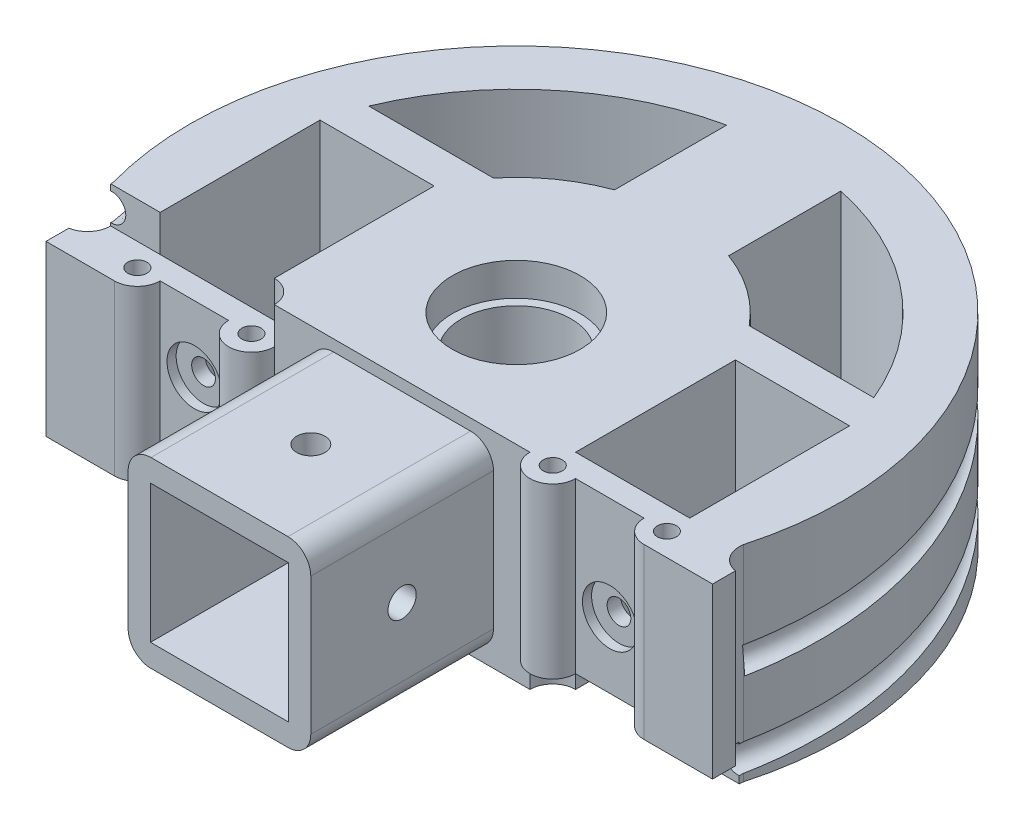
SolidWorks part; units mm, degrees
note: '?' marks a value the reader was unsure of.
ref_plane "Front Plane" through (0, 0, 0) normal (0, 0, 1) x (1, 0, 0)
ref_plane "Top Plane" through (0, 0, 0) normal (0, 1, 0) x (1, 0, 0)
ref_plane "Right Plane" through (0, 0, 0) normal (1, 0, 0) x (0, 0, -1)
sketch "Sketch1" plane through (0, 0, 0) normal (0, 1, 0) x (1, 0, 0)
  line L0 (0, 0) -> (-17.6777, -17.6777) construction
  line L1 (-17.6777, -17.6777) -> (-62.3934, 27.0381)
  line L2 (0, 68) -> (0, 0) construction
  line L3 (-38.8909, 3.5355) -> (30.8465, 73.2729) construction
  line L4 (-56.5685, 21.2132) -> (9.0638, 86.8455) construction
  line L5 (17.6777, -17.6777) -> (62.3934, 27.0381)
  line L6 (-51.6188, 26.163) -> (-33.9411, 8.4853)
  line L7 (-51.6188, 26.163) -> (-33.9411, 43.8406)
  line L8 (-33.9411, 8.4853) -> (-16.2635, 26.163)
  line L9 (-33.9411, 43.8406) -> (-16.2635, 26.163)
  line L10 (51.6188, 26.163) -> (33.9411, 43.8406)
  line L11 (51.6188, 26.163) -> (33.9411, 8.4853)
  line L12 (33.9411, 8.4853) -> (16.2635, 26.163)
  line L13 (33.9411, 43.8406) -> (16.2635, 26.163)
  circle A0 centre (0, 0) radius 68
  circle A1 centre (0, 0) radius 14.05
  circle A2 centre (0, 0) radius 25
  dimension "D1" = 136
  dimension "D2" = 28.1
  dimension "D3" = 50
  dimension "D4" = 30
  dimension "D5" = 25
  dimension "D6" = 7
  dimension "D7" = 25
  dimension "D8" = 25
extrude "Boss-Extrude1" add sketch "Sketch1" along normal blind 45 contours A2 A1 | A2 L5 A0 L1 L7 L9 L8 L6 L13 L10 L11 L12
sketch "Sketch2" plane through (0, 45, 0) normal (0, 1, 0) x (1, 0, 0)
  line L0 (-51.6188, 26.163) -> (-23.3345, 54.4472)
  line L1 (-51.6188, 26.163) -> (-33.9411, 8.4853)
  line L2 (-33.9411, 8.4853) -> (-5.6569, 36.7696)
  line L3 (-5.6569, 36.7696) -> (-23.3345, 54.4472)
  line L4 (0, 68) -> (0, -25) construction
  line L5 (33.9411, 8.4853) -> (5.6569, 36.7696)
  line L6 (51.6188, 26.163) -> (33.9411, 8.4853)
  line L7 (51.6188, 26.163) -> (23.3345, 54.4472)
  line L8 (5.6569, 36.7696) -> (23.3345, 54.4472)
  arc A0 (62.3934, 27.0381) -> (-62.3934, 27.0381) centre (0, 0) ccw construction
  arc A1 (-17.6777, -17.6777) -> (17.6777, -17.6777) centre (0, 0) ccw construction
  dimension "D1" = 40
  dimension "D2" = 40
extrude "Cut-Extrude1" cut sketch "Sketch2" against normal blind 45
sketch "Sketch3" plane through (0, 45, 0) normal (0, 1, 0) x (1, 0, 0)
  line L0 (-20.5061, 51.6188) -> (-48.7904, 23.3345)
  line L1 (-5.6569, 36.7696) -> (-23.3345, 54.4472) construction
  line L2 (-51.6188, 26.163) -> (-33.9411, 8.4853) construction
  line L3 (-48.7904, 23.3345) -> (-51.6188, 26.163)
  line L4 (-51.6188, 26.163) -> (-23.3345, 54.4472)
  line L5 (-23.3345, 54.4472) -> (-20.5061, 51.6188)
  line L6 (-33.9411, 8.4853) -> (-36.7696, 11.3137)
  line L7 (-36.7696, 11.3137) -> (-8.4853, 39.598)
  line L8 (-8.4853, 39.598) -> (-5.6569, 36.7696)
  line L9 (-5.6569, 36.7696) -> (-33.9411, 8.4853)
  line L10 (0, 68) -> (0, -25) construction
  line L11 (8.4853, 39.598) -> (5.6569, 36.7696)
  line L12 (36.7696, 11.3137) -> (8.4853, 39.598)
  line L13 (33.9411, 8.4853) -> (36.7696, 11.3137)
  line L14 (5.6569, 36.7696) -> (33.9411, 8.4853)
  line L15 (51.6188, 26.163) -> (23.3345, 54.4472)
  line L16 (48.7904, 23.3345) -> (51.6188, 26.163)
  line L17 (20.5061, 51.6188) -> (48.7904, 23.3345)
  line L18 (23.3345, 54.4472) -> (20.5061, 51.6188)
  arc A0 (62.3934, 27.0381) -> (-62.3934, 27.0381) centre (0, 0) ccw construction
  arc A1 (-17.6777, -17.6777) -> (17.6777, -17.6777) centre (0, 0) ccw construction
  dimension "D1" = 4
  dimension "D2" = 4
extrude "Boss-Extrude2" add sketch "Sketch3" against normal blind 45
chamfer "Chamfer1" distance 4 angle 45 4 edges at (34.6482, 45, -37.4767) (22.6274, 45, -25.4558) (-22.6274, 45, -25.4558) (-34.6482, 45, -37.4767)
chamfer "Chamfer2" distance 4 angle 45 4 edges at (34.6482, 0, -37.4767) (22.6274, 0, -25.4558) (-22.6274, 0, -25.4558) (-34.6482, 0, -37.4767)
sketch "Sketch5" plane through (0, 45, 0) normal (0, 1, 0) x (1, 0, 0)
  line L0 (-48.4659, 29.3158) -> (-68.4772, 9.3045) construction
  line L1 (-51.6188, 26.163) -> (-23.3345, 54.4472) construction
  line L2 (-30.0213, 12.4051) -> (-51.4271, -9.0007) construction
  line L3 (-5.6569, 36.7696) -> (-33.9411, 8.4853) construction
  line L4 (-17.6777, -17.6777) -> (-62.3934, 27.0381) construction
  line L5 (-42.78, 17.3241) -> (-61.4892, -1.3852) construction
  line L6 (-51.6188, 26.163) -> (-33.9411, 8.4853) construction
  line L7 (0, 68) -> (0, 30.851) construction
  circle A0 centre (-57.9828, 22.6274) radius 5
  circle A1 centre (-37.4767, 2.1213) radius 5
  arc A2 (62.3934, 27.0381) -> (-62.3934, 27.0381) centre (0, 0) ccw construction
  circle A3 centre (37.4767, 2.1213) radius 5
  circle A4 centre (57.9828, 22.6274) radius 5
  dimension "D1" = 10
  dimension "D2" = 2
extrude "Boss-Extrude4" add sketch "Sketch5" against normal up to surface (45 mm away) contours A0 | A1 | A4 | A3 up to face at (28.6378, 0, -31.4663)
sketch "Sketch6" plane through (0, 45, 0) normal (0, 1, 0) x (1, 0, 0)
  line L0 (-61.5183, 26.163) -> (-65.7609, 30.4056)
  line L1 (-65.7609, 30.4056) -> (-63.9013, 33.947)
  line L2 (-55.3925, 39.442) -> (-61.5183, 26.163)
  line L3 (0, 68) -> (0, 0) construction
  line L4 (65.7609, 30.4056) -> (63.9013, 33.947)
  line L5 (61.5183, 26.163) -> (65.7609, 30.4056)
  line L6 (55.3925, 39.442) -> (61.5183, 26.163)
  arc A0 (-63.9013, 33.947) -> (-55.3925, 39.442) centre (-66.3939, 47.142) ccw
  arc A1 (62.3934, 27.0381) -> (-62.3934, 27.0381) centre (0, 0) ccw construction
  arc A2 (63.9013, 33.947) -> (55.3925, 39.442) centre (66.3939, 47.142) cw
  dimension "D1" = 6
  dimension "D2" = 4
extrude "Boss-Extrude5" add sketch "Sketch6" against normal up to surface (45 mm away) contours L2 L0 L1 A0 | A2 L6 L5 L4 up to face at (0, 0, -11.4344)
sketch "Sketch7" plane through (0, 45, 0) normal (0, 1, 0) x (1, 0, 0)
  circle A0 centre (-57.9828, 22.6274) radius 2.1
  circle A1 centre (-37.4767, 2.1213) radius 2.1
  circle A3 centre (57.9828, 22.6274) radius 2.1
  circle A4 centre (37.4767, 2.1213) radius 2.1
  dimension "D1" = 4.2
  dimension "D2" = 4.2
  dimension "D3" = 4.2
  dimension "D4" = 4.2
extrude "Cut-Extrude2" cut sketch "Sketch7" against normal blind 45
sketch "Sketch9" plane through (0, 45, 0) normal (0, 1, 0) x (1, 0, 0)
  line L0 (34.4309, 8.975) -> (63.6627, 38.2069)
  line L1 (63.6627, 38.2069) -> (69.3196, 32.55)
  line L2 (69.3196, 32.55) -> (61.5183, 26.163)
  line L3 (54.4472, 19.0919) -> (42.78, 7.4246)
  line L4 (41.0122, 5.6569) -> (54.4472, 19.0919) construction
  line L5 (0, 68) -> (0, 24.5845) construction
  line L6 (-54.4472, 19.0919) -> (-42.78, 7.4246)
  line L7 (-69.3196, 32.55) -> (-61.5183, 26.163)
  line L8 (-63.6627, 38.2069) -> (-69.3196, 32.55)
  line L9 (-34.4309, 8.975) -> (-63.6627, 38.2069)
  arc A0 (34.4309, 8.975) -> (42.78, 7.4246) centre (37.4767, 2.1213) ccw
  arc A1 (54.4472, 19.0919) -> (61.5183, 26.163) centre (57.9828, 22.6274) ccw
  arc A2 (55.3925, 39.442) -> (-55.3925, 39.442) centre (0, 0) ccw construction
  arc A3 (-34.4309, 8.975) -> (-42.78, 7.4246) centre (-37.4767, 2.1213) cw
  arc A4 (-54.4472, 19.0919) -> (-61.5183, 26.163) centre (-57.9828, 22.6274) cw
  dimension "D1" = 15
  dimension "D2" = 8
extrude "Cut-Extrude5" cut sketch "Sketch9" against normal blind 4
sketch "Sketch10" plane through (0, 0, 0) normal (0, -1, 0) x (-1, 0, 0)
  line L0 (-34.4309, 8.975) -> (-64.7535, 39.2977)
  line L1 (-64.7535, 39.2977) -> (-71.1522, 32.899)
  line L2 (-71.1522, 32.899) -> (-62.9828, 22.6274)
  line L3 (-44.543, 4.6348) -> (-57.554, 17.6458)
  line L4 (0, -25) -> (0, 8.975) construction
  line L5 (71.1522, 32.899) -> (62.9828, 22.6274)
  line L6 (64.7535, 39.2977) -> (71.1522, 32.899)
  line L7 (34.4309, 8.975) -> (64.7535, 39.2977)
  line L8 (44.543, 4.6348) -> (57.554, 17.6458)
  arc A0 (-44.543, 4.6348) -> (-34.4309, 8.975) centre (-37.4767, 2.1213) ccw
  arc A1 (-62.9828, 22.6274) -> (-57.554, 17.6458) centre (-57.9828, 22.6274) ccw
  arc A4 (-17.6777, -17.6777) -> (17.6777, -17.6777) centre (0, 0) ccw construction
  arc A5 (44.543, 4.6348) -> (34.4309, 8.975) centre (37.4767, 2.1213) cw
  arc A6 (62.9828, 22.6274) -> (57.554, 17.6458) centre (57.9828, 22.6274) cw
  dimension "D2" = 15
extrude "Cut-Extrude6" cut sketch "Sketch10" against normal blind 4
sketch "Sketch11" plane through (0, 45, 0) normal (0, 1, 0) x (1, 0, 0)
  line L0 (0, -25) -> (0, 68) construction
  line L1 (-5.6569, 36.7696) -> (5.6569, 36.7696) construction
  line L2 (0, 39.598) -> (-17.1131, 56.711)
  line L3 (-5.6569, 36.7696) -> (-23.3345, 54.4472) construction
  line L4 (0, 39.598) -> (17.1131, 56.711)
  arc A0 (-17.6777, -17.6777) -> (17.6777, -17.6777) centre (0, 0) ccw construction
  arc A1 (55.3925, 39.442) -> (-55.3925, 39.442) centre (0, 0) ccw construction
  arc A2 (17.1131, 56.711) -> (-17.1131, 56.711) centre (0, 0) ccw
  dimension "D1" = 6
extrude "Cut-Extrude8" cut sketch "Sketch11" against normal through all
sketch "Sketch13" plane through (17.6777, 0, 17.6777) normal (0.7071, 0, 0.7071) x (0.7071, 0, -0.7071)
  line L0 (33, 22.5) -> (52, 22.5) construction
  line L1 (33, 41) -> (33, 4) construction
  line L2 (52, 41) -> (52, 4) construction
  circle A0 centre (42.5, 22.5) radius 2.6
  dimension "D1" = 5.2
extrude "Cut-Extrude9" cut sketch "Sketch13" against normal blind 59
sketch "Sketch14" plane through (17.6777, 0, 17.6777) normal (0.7071, 0, 0.7071) x (0.7071, 0, -0.7071)
  circle A0 centre (42.5, 22.5) radius 6.25
  dimension "D1" = 12.5
extrude "Cut-Extrude10" cut sketch "Sketch14" against normal blind 2
sketch "Sketch15" plane through (-19.799, 0, -19.799) normal (-0.7071, 0, -0.7071) x (-0.7071, 0, 0.7071)
  circle A0 centre (-42.5, 22.5) radius 6.25
  dimension "D1" = 12.5
extrude "Cut-Extrude11" cut sketch "Sketch15" against normal blind 2
sketch "Sketch16" plane through (-17.6777, 0, 17.6777) normal (-0.7071, 0, 0.7071) x (0.7071, 0, 0.7071)
  line L0 (-42.5, 41) -> (-42.5, 4) construction
  line L1 (-52, 41) -> (-33, 41) construction
  line L2 (-33, 4) -> (-52, 4) construction
  circle A0 centre (-42.5, 22.5) radius 2.6
  dimension "D1" = 5.2
extrude "Cut-Extrude12" cut sketch "Sketch16" against normal blind 58
sketch "Sketch17" plane through (-17.6777, 0, 17.6777) normal (-0.7071, 0, 0.7071) x (0.7071, 0, 0.7071)
  circle A0 centre (-42.5, 22.5) radius 6.25
  dimension "D1" = 12.5
extrude "Cut-Extrude13" cut sketch "Sketch17" against normal blind 2
sketch "Sketch18" plane through (19.799, 0, -19.799) normal (0.7071, 0, -0.7071) x (-0.7071, 0, -0.7071)
  circle A0 centre (42.5, 22.5) radius 6.25
  dimension "D1" = 12.5
extrude "Cut-Extrude14" cut sketch "Sketch18" against normal blind 2
sketch "Sketch19" plane through (0, 0, 0) normal (0, -1, 0) x (-1, 0, 0)
  circle A0 centre (0, 0) radius 14.05
  circle A1 centre (0, 0) radius 11
  dimension "D1" = 22
extrude "Boss-Extrude7" add sketch "Sketch19" against normal up to surface (45 mm away) up to face at (0, 45, -51.8486)
sketch "Sketch20" plane through (0, 45, 0) normal (0, 1, 0) x (1, 0, 0)
  circle A0 centre (0, 0) radius 14.1
  dimension "D1" = 28.2
extrude "Cut-Extrude15" cut sketch "Sketch20" against normal blind 7.2
sketch "Sketch21" plane through (0, 0, 0) normal (0, -1, 0) x (-1, 0, 0)
  circle A0 centre (0, 0) radius 14.1
  dimension "D1" = 28.2
extrude "Cut-Extrude16" cut sketch "Sketch21" against normal blind 7.2
ref_plane "Plane1" through (0, 0, 25) normal (0, 0, 1) x (1, 0, 0)
sketch "Sketch22" plane through (0, 0, 25) normal (0, 0, 1) x (1, 0, 0)
  line L0 (0, 0) -> (0, 45) construction
  line L1 (17.6777, 45) -> (-17.6777, 45) construction
  line L3 (-20, 2.5) -> (20, 2.5)
  line L4 (-15.1, 7.4) -> (15.1, 7.4)
  line L5 (-15.1, 7.4) -> (-15.1, 37.6)
  line L6 (-15.1, 37.6) -> (15.1, 37.6)
  line L7 (15.1, 7.4) -> (15.1, 37.6)
  line L8 (-15.1, 7.4) -> (15.1, 37.6) construction
  line L9 (-15.1, 37.6) -> (15.1, 7.4) construction
  line L10 (-20, 2.5) -> (-20, 42.5)
  line L11 (-20, 42.5) -> (20, 42.5)
  line L12 (20, 2.5) -> (20, 42.5)
  line L13 (-20, 2.5) -> (20, 42.5) construction
  line L14 (-20, 42.5) -> (20, 2.5) construction
  point P5 (0, 22.5)
  point P6 (0, 22.5)
  dimension "D1" = 30.2
  dimension "D2" = 30.2
  dimension "D3" = 40
  dimension "D4" = 40
extrude "Boss-Extrude8" add sketch "Sketch22" along normal blind 40 separate body
sketch "Sketch23" plane through (0, 0, 25) normal (0, 0, -1) x (-1, 0, 0)
  line L0 (0, 45) -> (0, 0) construction
  line L2 (-20, 2.5) -> (20, 2.5)
  line L3 (-15.1, 7.4) -> (15.1, 7.4)
  line L4 (-15.1, 7.4) -> (-15.1, 37.6)
  line L5 (-15.1, 37.6) -> (15.1, 37.6)
  line L6 (15.1, 7.4) -> (15.1, 37.6)
  line L7 (-15.1, 7.4) -> (15.1, 37.6) construction
  line L8 (-15.1, 37.6) -> (15.1, 7.4) construction
  line L9 (-20, 2.5) -> (-20, 42.5)
  line L10 (-20, 42.5) -> (20, 42.5)
  line L11 (20, 2.5) -> (20, 42.5)
  line L12 (-20, 2.5) -> (20, 42.5) construction
  line L13 (-20, 42.5) -> (20, 2.5) construction
  point P4 (0, 22.5)
  point P5 (0, 22.5)
  dimension "D1" = 30.2
  dimension "D2" = 30.2
  dimension "D3" = 40
  dimension "40" = 40
extrude "Boss-Extrude9" add sketch "Sketch23" along normal blind 10
fillet "Fillet3" radius 5 4 edges at (-20, 2.5, 40.1777) (-20, 42.5, 40.1777) (20, 2.5, 40.1777) (20, 42.5, 40.1777)
sketch "Sketch24" plane through (0, 42.5, 0) normal (0, 1, 0) x (1, 0, 0)
  line L0 (0, -25) -> (0, -65) construction
  line L1 (15, -65) -> (-15, -65) construction
  arc A0 (-17.6777, -17.6777) -> (17.6777, -17.6777) centre (0, 0) ccw construction
  circle A1 centre (0, -45) radius 3.1
  dimension "D1" = 6.2
extrude "Cut-Extrude17" cut sketch "Sketch24" against normal blind 42
sketch "Sketch25" plane through (-20, 0, 0) normal (-1, 0, 0) x (0, 0, 1)
  line L0 (25, 42.5) -> (25, 2.5) construction
  line L1 (65, 2.5) -> (20, 2.5) construction
  line L2 (25, 22.5) -> (65, 22.5) construction
  line L3 (65, 37.5) -> (65, 7.5) construction
  circle A0 centre (45, 22.5) radius 3.1
  dimension "D1" = 6.2
extrude "Cut-Extrude18" cut sketch "Sketch25" against normal blind 42
sketch "Sketch26" plane through (0, 0, 25) normal (0, 0, 1) x (1, 0, 0)
  line L0 (0, 37.6) -> (0, 7.4) construction
  line L1 (15.1, 37.6) -> (-15.1, 37.6) construction
  line L2 (-15.1, 7.4) -> (15.1, 7.4) construction
  line L4 (-15.1, 7.4) -> (15.1, 7.4)
  line L5 (-15.1, 7.4) -> (-15.1, 37.6)
  line L6 (-15.1, 37.6) -> (15.1, 37.6)
  line L7 (15.1, 7.4) -> (15.1, 37.6)
  line L8 (-15.1, 7.4) -> (15.1, 37.6) construction
  line L9 (-15.1, 37.6) -> (15.1, 7.4) construction
  point P6 (0, 22.5)
extrude "Boss-Extrude10" add sketch "Sketch26" against normal blind 8
sketch "Sketch27" plane through (0, 0, 0) normal (0, -1, 0) x (-1, 0, 0)
  circle A0 centre (0, 0) radius 14.1
  circle A1 centre (0, 0) radius 14
  dimension "D1" = 28
extrude "Boss-Extrude11" add sketch "Sketch27" against normal up to surface (45 mm away) up to face at (0, 45, 14.1)
sketch "Sketch28" plane through (0, 7.2, 0) normal (0, -1, 0) x (-1, 0, 0)
  circle A0 centre (0, 0) radius 7.5
  circle A1 centre (0, 0) radius 11
  dimension "D1" = 15
extrude "Boss-Extrude12" add sketch "Sketch28" against normal up to surface (30.6 mm away) contours A1 | A0 up to face at (0, 37.8, 11)
sketch "Sketch29" plane through (0, 45, 0) normal (0, 1, 0) x (1, 0, 0)
  line L0 (0, -25) -> (-66.9869, -25)
  line L1 (0, -25) -> (66.9869, -25)
  arc A0 (66.9869, -25) -> (-66.9869, -25) centre (0, 0) ccw
  circle A1 centre (0, 0) radius 14
  arc A2 (-15, -20) -> (15, -20) centre (0, 0) ccw construction
  dimension "D1" = 143
extrude "Boss-Extrude13" add sketch "Sketch29" against normal up to surface (45 mm away) up to face at (0, 0, -51.8486)
sketch "Sketch30" plane through (0, 45, 0) normal (0, 1, 0) x (1, 0, 0)
  circle A0 centre (0, 0) radius 71.5
  circle A1 centre (0, 0) radius 76.6476
extrude "Cut-Extrude19" cut sketch "Sketch30" against normal blind 60
sketch "Sketch32" plane through (0, 45, 0) normal (0, 1, 0) x (1, 0, 0)
  line L0 (-66.9869, -25) -> (66.9869, -25) construction
  line L1 (0, 71.5) -> (0, 18.8143) construction
  circle A0 centre (-57.9869, -25) radius 5
  circle A1 centre (-57.9869, -25) radius 2.1
  circle A2 centre (-36.9621, -25) radius 5
  circle A3 centre (-36.9621, -25) radius 2.1
  arc A4 (66.9869, -25) -> (-66.9869, -25) centre (0, 0) ccw construction
  circle A5 centre (36.9621, -25) radius 2.1
  circle A6 centre (36.9621, -25) radius 5
  circle A7 centre (57.9869, -25) radius 5
  circle A8 centre (57.9869, -25) radius 2.1
  dimension "D1" = 10
  dimension "D2" = 4.2
  dimension "D3" = 9
  dimension "D4" = 10
  dimension "D5" = 4.2
extrude "Boss-Extrude14" add sketch "Sketch32" against normal up to surface (45 mm away) up to face at (0, 0, -23.25)
sketch "Sketch33" plane through (0, 45, 0) normal (0, 1, 0) x (1, 0, 0)
  line L2 (-44.8112, -25) -> (-29.4135, -25)
  line L3 (-52.9869, -25) -> (-41.9621, -25) construction
  line L4 (-31.9621, -25) -> (31.9621, -25) construction
  line L5 (-29.4135, -25) -> (-29.4135, -32.7766)
  line L6 (-29.4135, -32.7766) -> (-44.8112, -32.7766)
  line L7 (-44.8112, -32.7766) -> (-44.8112, -25)
  line L8 (27.242, -25) -> (44.8112, -25)
  line L9 (41.9621, -25) -> (52.9869, -25) construction
  line L10 (44.8112, -25) -> (44.8112, -32.7766)
  line L11 (44.8112, -32.7766) -> (27.242, -32.7766)
  line L12 (27.242, -32.7766) -> (27.242, -25)
extrude "Cut-Extrude23" cut sketch "Sketch33" against normal blind 60
sketch "Sketch38" plane through (0, 45, 0) normal (0, 1, 0) x (1, 0, 0)
  line L0 (-60.0869, -25) -> (-55.8869, -25) construction
  line L1 (55.8869, -25) -> (60.0869, -25) construction
  line L2 (-57.9869, -25) -> (-32.9869, -25) construction
  line L3 (-52.9869, -25) -> (52.9869, -25) construction
  line L4 (0, -25) -> (0, -16.3919) construction
  circle A0 centre (-57.9869, -25) radius 5
  circle A1 centre (57.9869, -25) radius 5
  circle A2 centre (-32.9869, -25) radius 5
  circle A3 centre (32.9869, -25) radius 5
  dimension "D2" = 10
  dimension "D1" = 25
extrude "Boss-Extrude18" add sketch "Sketch38" against normal up to surface (45 mm away) up to face at (57.9869, 0, 26.05)
sketch "Sketch39" plane through (0, 45, 0) normal (0, 1, 0) x (1, 0, 0)
  circle A0 centre (-57.9869, -25) radius 2.1
  circle A1 centre (-32.9869, -25) radius 2.1
  circle A2 centre (32.9869, -25) radius 2.1
  circle A3 centre (57.9869, -25) radius 2.1
  dimension "D1" = 4.2
  dimension "D2" = 4.2
  dimension "D3" = 4.2
  dimension "D4" = 4.2
extrude "Cut-Extrude24" cut sketch "Sketch39" against normal blind 60
sketch "Sketch40" plane through (0, 45, 0) normal (0, 1, 0) x (1, 0, 0)
  line L0 (-57.9869, -25) -> (-57.9869, 7.5034) construction
  line L1 (-32.9869, -25) -> (-32.9869, 7.5034) construction
  line L2 (-52.9869, -25) -> (-37.9869, -25) construction
  line L3 (-57.9869, -20) -> (-32.9869, -20)
  line L4 (-57.9869, -20) -> (-57.9869, 15)
  line L5 (-57.9869, 15) -> (-32.9869, 15)
  line L6 (-32.9869, -20) -> (-32.9869, 15)
  line L7 (0, -25) -> (0, -2.7956) construction
  line L8 (-27.9869, -25) -> (27.9869, -25) construction
  line L9 (57.9869, 15) -> (32.9869, 15)
  line L10 (32.9869, -20) -> (32.9869, 15)
  line L11 (57.9869, -20) -> (32.9869, -20)
  line L12 (57.9869, -20) -> (57.9869, 15)
  dimension "D1" = 5
  dimension "D2" = 35
extrude "Cut-Extrude25" cut sketch "Sketch40" against normal blind 60
sketch "Sketch42" plane through (0, 45, 0) normal (0, 1, 0) x (1, 0, 0)
  line L0 (-32.9869, 15) -> (-32.9869, 23) construction
  line L1 (-32.9869, 23) -> (-28.0025, 23)
  line L3 (-28.0025, 23) -> (-55.3036, 23)
  line L4 (0, 0) -> (0, 65.5316) construction
  line L5 (-28.0025, 23) -> (55.3036, 23)
  circle A0 centre (0, 0) radius 59.8956
  circle A2 centre (0, 0) radius 36.2372
  dimension "D1" = 8
extrude "Cut-Extrude27" cut sketch "Sketch42" against normal blind 60 contours A2 L5 A0 L3 L1
sketch "Sketch43" plane through (0, 0, 25) normal (0, 0, 1) x (1, 0, 0)
  line L0 (-45.4869, 45) -> (-45.4869, 0) construction
  line L1 (-52.9869, 45) -> (-37.9869, 45) construction
  line L2 (-37.9869, 0) -> (-52.9869, 0) construction
  line L3 (0, 37.6) -> (0, 7.4) construction
  line L4 (15.1, 37.6) -> (-15.1, 37.6) construction
  line L5 (-15.1, 7.4) -> (15.1, 7.4) construction
  circle A0 centre (-45.4869, 22.5) radius 2.6
  circle A1 centre (45.4869, 22.5) radius 2.6
  dimension "D1" = 5.2
extrude "Cut-Extrude28" cut sketch "Sketch43" against normal blind 53
sketch "Sketch46" plane through (0, 0, -23) normal (0, 0, -1) x (-1, 0, 0)
  circle A0 centre (45.4869, 22.5) radius 6
  circle A1 centre (-45.4869, 22.5) radius 6
  dimension "D1" = 12
  dimension "D2" = 12
extrude "Cut-Extrude29" cut sketch "Sketch46" against normal blind 5
sketch "Sketch47" plane through (0, 0, 25) normal (0, 0, 1) x (1, 0, 0)
  circle A0 centre (45.4869, 22.5) radius 6
  circle A1 centre (-45.4869, 22.5) radius 6
  dimension "D1" = 12
  dimension "D2" = 12
extrude "Cut-Extrude30" cut sketch "Sketch47" against normal blind 2
sketch "Sketch48" plane through (0, 45, 0) normal (0, 1, 0) x (1, 0, 0)
  line L0 (0, 36.2372) -> (0, 61.3861) construction
  line L1 (-12.5, 34.0131) -> (-12.5, 58.5767)
  line L2 (12.5, 34.0131) -> (12.5, 58.5767)
  arc A0 (28.0025, 23) -> (-28.0025, 23) centre (0, 0) ccw construction
  arc A1 (55.3036, 23) -> (-55.3036, 23) centre (0, 0) ccw construction
  arc A2 (12.5, 58.5767) -> (-12.5, 58.5767) centre (0, 0) ccw
  arc A3 (12.5, 34.0131) -> (-12.5, 34.0131) centre (0, 0) ccw
  dimension "D1" = 25
extrude "Boss-Extrude19" add sketch "Sketch48" against normal up to surface (45 mm away) up to face at (0, 0, -14)
sketch "Sketch49" plane through (0, 45, 0) normal (0, 1, 0) x (1, 0, 0)
  line L0 (-57.9869, -30) -> (-72.9869, -30)
  line L1 (-72.9869, -30) -> (-72.9869, -25)
  line L2 (-66.336, -25) -> (-62.9869, -25)
  line L3 (0, -14) -> (0, -25) construction
  line L4 (-27.9869, -25) -> (27.9869, -25) construction
  line L8 (-68.8967, -19.1178) -> (-66.336, -25)
  line L9 (57.9869, -30) -> (72.9869, -30)
  line L10 (66.336, -25) -> (62.9869, -25)
  line L11 (68.8967, -19.1178) -> (66.336, -25)
  line L12 (72.9869, -30) -> (72.9869, -25)
  arc A0 (-62.9869, -25) -> (-52.9869, -25) centre (-57.9869, -25) ccw construction
  arc A1 (-62.9869, -25) -> (-57.9869, -30) centre (-57.9869, -25) ccw
  circle A2 centre (0, 0) radius 14 construction
  circle A3 centre (0, 0) radius 14 construction
  arc A5 (-72.9869, -25) -> (-68.8967, -19.1178) centre (-73.883, -20.0138) ccw
  arc A6 (66.9869, -25) -> (-66.9869, -25) centre (0, 0) ccw construction
  arc A7 (62.9869, -25) -> (57.9869, -30) centre (57.9869, -25) cw
  arc A8 (72.9869, -25) -> (68.8967, -19.1178) centre (73.883, -20.0138) cw
  dimension "D1" = 15
extrude "Boss-Extrude20" add sketch "Sketch49" against normal up to surface (45 mm away) up to face at (-28.3562, 0, -36.2247)
sketch "Sketch50" plane through (0, 45, 0) normal (0, 1, 0) x (1, 0, 0)
  line L0 (0, -14) -> (0, -25) construction
  line L1 (-32.9869, -20) -> (-80.5094, -20)
  line L2 (-32.9869, -30) -> (-32.9869, -36.5273)
  line L3 (-32.9869, -36.5273) -> (-80.5094, -36.5273)
  line L4 (-80.5094, -20) -> (-80.5094, -36.5273)
  line L5 (15, -25) -> (-15, -25) construction
  arc A0 (-32.9869, -30) -> (-32.9869, -20) centre (-32.9869, -25) ccw
  circle A1 centre (0, 0) radius 14 construction
extrude "Cut-Extrude31" cut sketch "Sketch50" against normal blind 8
sketch "Sketch51" plane through (0, 0, 0) normal (0, -1, 0) x (1, 0, 0)
  line L1 (32.9869, 20) -> (85.1802, 20)
  line L2 (32.9869, 30) -> (32.9869, 38.9476)
  line L3 (32.9869, 38.9476) -> (85.1802, 38.9476)
  line L4 (85.1802, 20) -> (85.1802, 38.9476)
  arc A0 (32.9869, 30) -> (32.9869, 20) centre (32.9869, 25) ccw
extrude "Cut-Extrude32" cut sketch "Sketch51" against normal blind 8
ref_plane "Plane12" through (0, 41, 0) normal (0, 1, 0) x (1, 0, 0)
sketch "Sketch111" plane through (0, 41, 0) normal (0, 1, 0) x (1, 0, 0)
  circle A0 centre (0, 0) radius 71.5
curve "Helix/Spiral6" pitch 30 height 18 turns 0.6
sweep "Cut-Sweep16" cut path "Helix/Spiral6" align with end faces yes circular profile diameter 6 parameters "D3"=6
ref_plane "Plane13" through (68.8967, 23.1589, 19.1178) normal (0, 1, 0) x (1, 0, 0)
ref_plane "Plane15" through (0, 22.5, 0) normal (0, 1, 0) x (1, 0, 0)
sketch "Sketch133" plane through (0, 22.5, 0) normal (0, 1, 0) x (1, 0, 0)
  circle A0 centre (0, 0) radius 71.5
curve "Helix/Spiral7" pitch 30.5 height 18.3 turns 0.6
sweep "Cut-Sweep17" cut path "Helix/Spiral7" align with end faces yes circular profile diameter 6 parameters "D3"=6
sketch "Sketch134" plane through (0, 7.2, 0) normal (0, -1, 0) x (-1, 0, 0)
  circle A0 centre (0, 0) radius 12
  dimension "D1" = 24
extrude "Cut-Extrude33" cut sketch "Sketch134" against normal up to surface (30.6 mm away) up to face at (0, 37.8, 14)
ref_axis "Axis1" through (0, 0, 0) along (0, 1, 0)?
ref_plane "Plane4" through (0, 0, 0) normal (-1, 0, 0) x (0, 1, 0)
sketch3d "3DSketch4"
  line L0 (-68.8169, 44.3226, 20) -> (72.9869, 22.3272, 30)
  line L1 (-68.8169, 45, 20) -> (-68.8169, 43.6451, 20) construction
  line L2 (72.9869, 8, 30) -> (72.9869, 45, 30) construction
ref_plane "Plane6" through (5.0966, 32.8578, 0) normal (0.1533, 0.9882, 0) x (0.9858, -0.1529, 0.0695)
ref_plane "Plane10" through (0, 0, 0) normal (-1, 0, 0) x (0, 1, 0)
